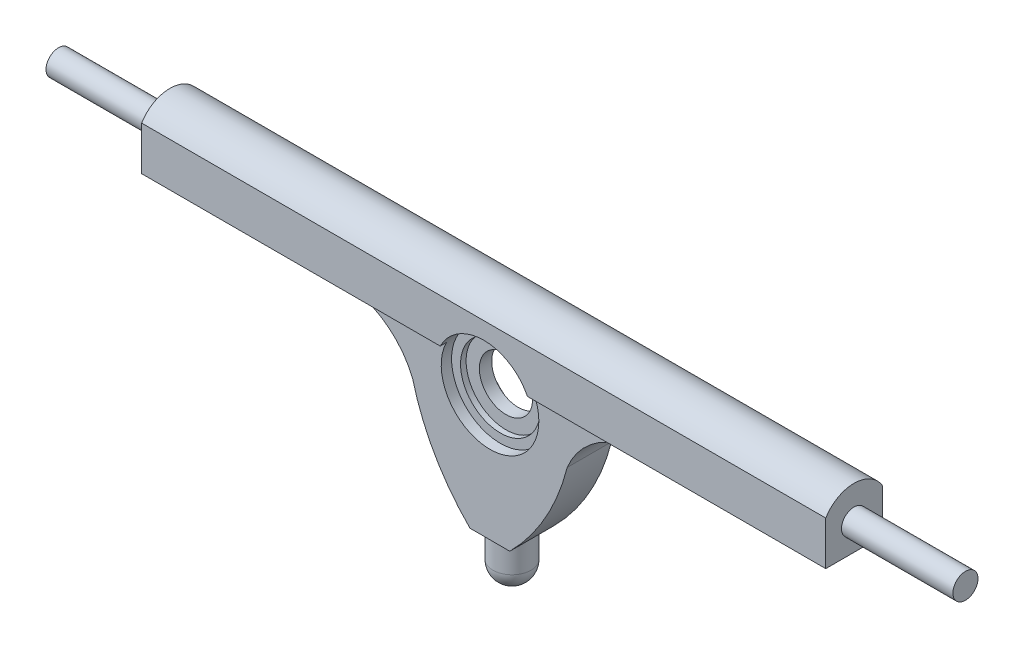
SolidWorks part; units mm, degrees
ref_plane "Front Plane" through (0, 0, 0) normal (0, 0, 1) x (1, 0, 0)
ref_plane "Top Plane" through (0, 0, 0) normal (0, 1, 0) x (1, 0, 0)
ref_plane "Right Plane" through (0, 0, 0) normal (1, 0, 0) x (0, 0, -1)
sketch "Sketch1" plane through (0, 0, 0) normal (1, 0, 0) x (0, 0, -1)
  line L1 (-9.017, -6.985) -> (9.017, -6.985)
  line L2 (-9.017, -6.985) -> (-9.017, 6.985)
  line L4 (9.017, -6.985) -> (9.017, 6.985)
  line L5 (-9.017, -6.985) -> (9.017, 6.985) construction
  line L6 (-9.017, 6.985) -> (9.017, -6.985) construction
  arc A0 (-9.017, 6.985) -> (9.017, 6.985) centre (0, 1.5224) cw
  point P0 (0, 0)
  point P7 (0, 12.065)
  dimension "D1" = 19.05
  dimension "D2" = 13.97
  dimension "D3" = 18.034
extrude "Boss-Extrude1" add sketch "Sketch1" along normal mid plane 218
sketch3d "3DSketch1"
  line L0 (0, -6.985, 0) -> (0, -54.483, 0) construction
  line L1 (-24.638, -22.225, 0) -> (0, -22.225, 0) construction
  line L2 (6.35, -54.483, 0) -> (-6.35, -54.483, 0)
  line L3 (-43.18, -6.985, 0) -> (43.18, -6.985, 0)
  arc A0 (-43.18, -6.985, 0) -> (-24.638, -22.225, 0) centre (-48.1235, -31.8993, 0) cw
  arc A1 (-24.638, -22.225, 0) -> (-6.35, -54.483, 0) centre (43.0905, -5.1407, 0) cw
  arc A2 (24.638, -22.225, 0) -> (6.35, -54.483, 0) centre (-43.0905, -5.1407, 0) ccw
  arc A3 (43.18, -6.985, 0) -> (24.638, -22.225, 0) centre (48.1235, -31.8993, 0) ccw
  point P7 (-48.1235, -31.8993, -25.4)
  point P10 (43.0905, -5.1407, 69.85)
  point P15 (-43.0905, -5.1407, -69.85)
  point P18 (48.1235, -31.8993, 25.4)
  dimension "D5" = 25.4
  dimension "D6" = 69.85
  dimension "D1" = 24.638
  dimension "D2" = 47.498
  dimension "D3" = 15.24
  dimension "D4" = 43.18
  dimension "D7" = 6.35
extrude "Boss-Extrude2" add sketch "3DSketch1" along direction (0, 0, -1) on the side of the normal mid plane 14.097
ref_plane "Plane1" through (0, 0, 0) normal (0, 0, 1) x (1, 0, 0)
sketch "Sketch8" plane through (0, 0, 0) normal (0, 0, 1) x (1, 0, 0)
  line L0 (0, -69.469) -> (0, -54.483)
  line L1 (-6.35, -54.483) -> (6.35, -54.483) construction
  line L2 (0, -54.483) -> (6.096, -54.483)
  line L3 (6.096, -54.483) -> (6.096, -63.373)
  line L4 (0, -47.1342) -> (0, -77.1544) construction
  arc A0 (6.096, -63.373) -> (0, -69.469) centre (0, -63.373) cw
  dimension "D1" = 8.89
  dimension "D2" = 6.096
revolve "Revolve2" add sketch "Sketch8" angle 360 about L4
sketch "Sketch9" plane through (0, 0, 7.0485) normal (0, 0, 1) x (1, 0, 0)
  circle A0 centre (0.0506, -13.9773) radius 4.6736
ref_plane "Plane2" through (0, -13.9773, 0) normal (0, -1, 0) x (-1, 0, 0)
sketch "Sketch10" plane through (0, -13.9773, 0) normal (0, -1, 0) x (-1, 0, 0)
  line L0 (-0.0506, -55.7699) -> (-0.0506, 64.4216) construction
  line L1 (-0.0506, -9.017) -> (-0.0506, 9.017)
  line L2 (19.1976, 0) -> (-22.9025, 0) construction
  line L4 (-0.0506, 9.017) -> (-15.6081, 9.017)
  line L5 (-15.6081, 9.017) -> (-15.6081, 3.7465)
  line L6 (-15.6081, 3.7465) -> (-12.7506, 3.7465)
  line L7 (-12.7506, 3.7465) -> (-12.7506, 1.9685)
  line L8 (-12.7506, 1.9685) -> (-8.5342, 1.9685)
  line L9 (-8.5342, 1.9685) -> (-8.5342, -1.9685)
  line L10 (-64.6711, 0) -> (64.6711, 0) construction
  line L12 (-0.0506, -9.017) -> (-15.6081, -9.017)
  line L13 (-15.6081, -9.017) -> (-15.6081, -3.7465)
  line L14 (-15.6081, -3.7465) -> (-12.7506, -3.7465)
  line L15 (-12.7506, -3.7465) -> (-12.7506, -1.9685)
  line L16 (-12.7506, -1.9685) -> (-8.5342, -1.9685)
  line L17 (-109, 9.017) -> (109, 9.017) construction
  point P5 (-0.0506, 0)
  point P23 (-8.5342, 0)
  dimension "D3" = 15.5575
  dimension "D4" = 12.7
  dimension "D5" = 8.4836
revolve "Cut-Revolve1" cut sketch "Sketch10" angle 360 about L0
sketch "Sketch11" plane through (109, 0, 0) normal (1, 0, 0) x (0, 0, -1)
  circle A0 centre (0, 1.5224) radius 4
  arc A1 (9.017, 6.985) -> (-9.017, 6.985) centre (0, 1.5224) ccw construction
  dimension "D1" = 8
extrude "Boss-Extrude3" add sketch "Sketch11" along normal blind 35.5
mirror "Mirror1" about plane through (0, 0, 0) normal (1, 0, 0) of "Boss-Extrude3"
